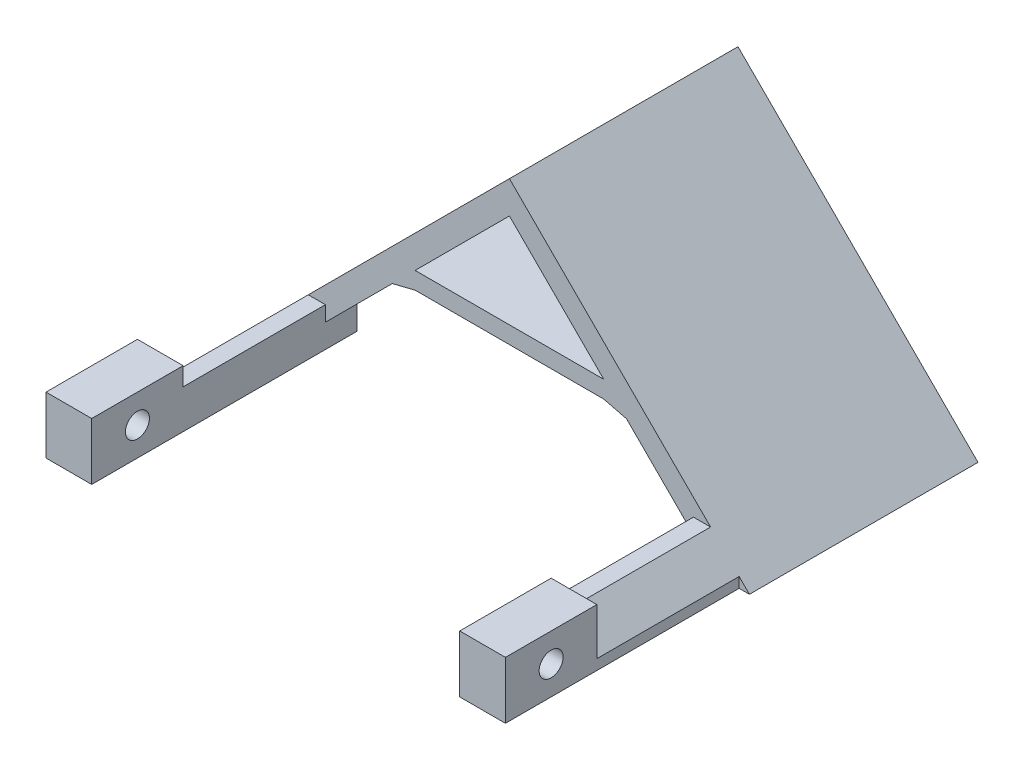
SolidWorks part; units mm, degrees
ref_plane "Front Plane" through (0, 0, 0) normal (0, 0, 1) x (1, 0, 0)
ref_plane "Top Plane" through (0, 0, 0) normal (0, 1, 0) x (1, 0, 0)
ref_plane "Right Plane" through (0, 0, 0) normal (1, 0, 0) x (0, 0, -1)
sketch "Sketch1" plane through (0, 0, 0) normal (0, 0, 1) x (1, 0, 0)
  line L1 (0, 0) -> (-42, -42)
  line L2 (0, -1000.3549) -> (0, 48999.6451) construction
  line L3 (-32.3431, -38) -> (-20.5, -26.1569)
  line L4 (32.3431, -38) -> (20.5, -26.1569)
  line L5 (0, 0) -> (42, -42)
  line L7 (-42, -42) -> (-16.5, -42) construction
  line L8 (-32.3431, -38) -> (-20.5, -38) construction
  line L9 (-34, -34) -> (34, -34) construction
  line L10 (-16.5, -42) -> (-16.5, -25.1569) construction
  line L11 (16.5, -42) -> (16.5, -25.1569) construction
  line L12 (16.5, -42) -> (42, -42) construction
  line L13 (20.5, -38) -> (32.3431, -38) construction
  line L14 (-20.5, -38) -> (-20.5, -26.1569) construction
  line L15 (20.5, -38) -> (20.5, -26.1569) construction
  line L16 (-16.5, -22.1569) -> (0, -5.6569)
  line L17 (16.5, -22.1569) -> (0, -5.6569)
  line L18 (16.5, -22.1569) -> (-16.5, -22.1569)
  line L19 (16.5, -25.1569) -> (-16.5, -25.1569)
  line L20 (-32.3431, -38) -> (-36.3431, -42)
  line L21 (-16.5, -25.1569) -> (-20.5, -26.1569)
  line L22 (16.5, -25.1569) -> (20.5, -26.1569)
  line L23 (32.3431, -38) -> (36.3431, -42)
  line L24 (-36.3431, -42) -> (-42, -42)
  line L25 (36.3431, -42) -> (42, -42)
  point P21 (0, -25.1569)
  dimension "D1" = 90
  dimension "D2" = 4
  dimension "D3" = 4
  dimension "D4" = 68
  dimension "D5" = 8
  dimension "D6" = 33
  dimension "D7" = 4
  dimension "D8" = 3
extrude "Boss-Extrude1" add sketch "Sketch1" along normal mid plane 40
sketch "Sketch5" plane through (0, 0, 20) normal (0, 0, 1) x (1, 0, 0)
  line L1 (0, 0) -> (-42, -42) construction
  line L2 (-35.2, -35.2) -> (-32.2, -35.2)
  line L3 (-32.2, -35.2) -> (-32.2, -42)
  line L5 (-32.2, -42) -> (-40.2, -42)
  line L6 (-40.2, -42) -> (-40.2, -40.2)
  line L7 (-40.2, -40.2) -> (-35.2, -35.2)
  line L8 (-40.4, 43.0678) -> (-40.4, -67) construction
  line L9 (-42, -42) -> (-36.3431, -42) construction
  point P8 (0, 0)
  dimension "D1" = 8
  dimension "D2" = 3
  dimension "D3" = 0.2
extrude "Boss-Extrude4" add sketch "Sketch5" along normal up to surface (24.9 mm away)
sketch "Sketch8" plane through (0, 0, 20) normal (0, 0, -1) x (-1, 0, 0)
  line L3 (32.2, -42) -> (36.3431, -42)
  line L4 (36.3431, -42) -> (32.2, -37.8569)
  line L5 (32.2, -37.8569) -> (32.2, -42)
  line L6 (32.2, -42) -> (36.3431, -42)
  line L7 (36.3431, -42) -> (32.2, -37.8569)
  line L8 (32.2, -37.8569) -> (32.2, -42)
  dimension "D1" = 0
extrude "Boss-Extrude6" add sketch "Sketch8" along normal blind 5.5
sketch "Sketch6" plane through (0, 0, 44.9) normal (0, 0, 1) x (1, 0, 0)
  line L0 (-40.2, -40.2) -> (-40.2, -42) construction
  line L1 (-32.2, -42) -> (-40.2, -42)
  line L2 (-32.2, -42) -> (-32.2, -32)
  line L3 (-32.2, -32) -> (-40.2, -32)
  line L4 (-40.2, -42) -> (-40.2, -32)
  line L5 (-32.2, -42) -> (-32.2, -35.2) construction
  line L6 (-40.2, -42) -> (-32.2, -42) construction
  dimension "D1" = 10
  dimension "D2" = 0
extrude "Boss-Extrude5" add sketch "Sketch6" along normal blind 16
sketch "Sketch7" plane through (-32.2, 0, 0) normal (1, 0, 0) x (0, 0, -1)
  line L0 (-60.9, -32) -> (-44.9, -32) construction
  line L1 (-60.9, -42) -> (-60.9, -32) construction
  circle A0 centre (-52.9, -37) radius 2.1
  point P5 (-52.9, -32)
  point P8 (-60.9, -37)
  dimension "D1" = 4.2
extrude "Cut-Extrude1" cut sketch "Sketch7" against normal through all
mirror "Mirror1" about plane through (0, 0, 0) normal (1, 0, 0) of "Boss-Extrude6", "Boss-Extrude4", "Boss-Extrude5", "Cut-Extrude1"
equation "\"width\"= 24"
equation "\"thk\"= 3"
equation "\"holesize\"= 4.2"
equation "\"holedistance\"= ( 20 + 12 ) / 2"
equation "\"threaded_hole\"= 3.9"
equation "\"fillet_radius\"= 2"
equation "\"ground_clearance\"= 25"
equation "\"tire_thk\"= 3"
equation "\"innerwheel_diam\" = \"wheel_diam\"-2*\"tire_thk\""
equation "\"innerwheel_thk\"= 8"
equation "\"wheel_diam\"= 2*(\"width\"/2+\"ground_clearance\")"
equation "\"coloursensor_holesize\"= 2.65"
equation "\"hole_to_edge\" = 4"
equation "\"D1@Sketch7\"=\"holesize\""
equation "\"D7@Sketch1\"=\"D2@Sketch1\""
